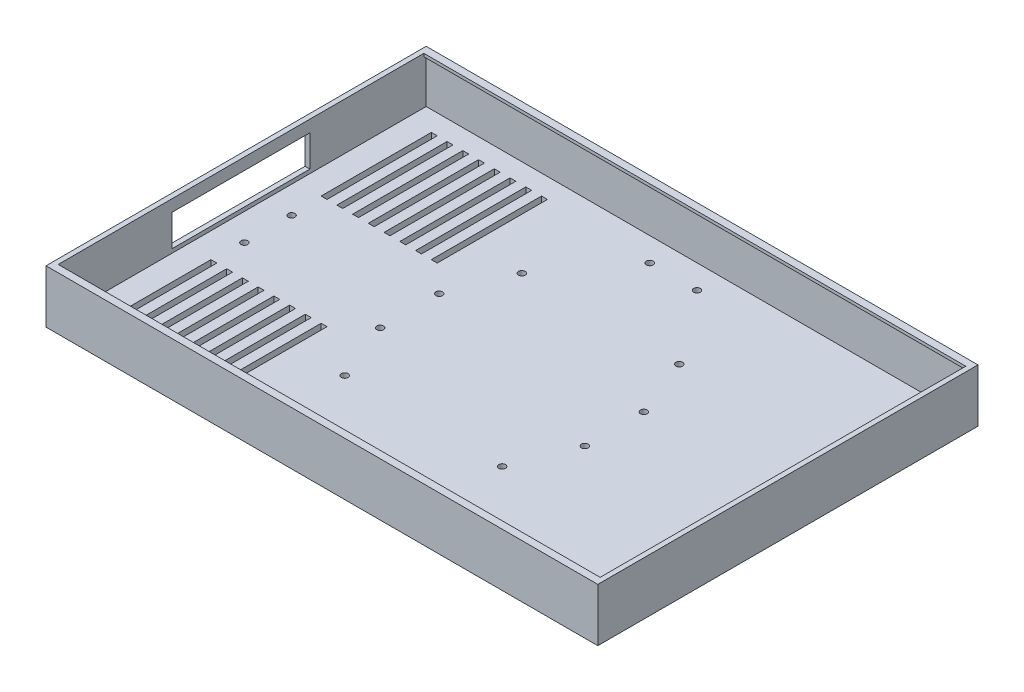
SolidWorks part; units mm, degrees
ref_plane "Front Plane" through (0, 0, 0) normal (0, 0, 1) x (1, 0, 0)
ref_plane "Top Plane" through (0, 0, 0) normal (0, 1, 0) x (1, 0, 0)
ref_plane "Right Plane" through (0, 0, 0) normal (1, 0, 0) x (0, 0, -1)
sketch "Sketch1" plane through (0, 0, 0) normal (0, 1, 0) x (1, 0, 0)
  line L1 (-140.2, -96.6) -> (140.2, -96.6)
  line L2 (-140.2, -96.6) -> (-140.2, 96.6)
  line L3 (-140.2, 96.6) -> (140.2, 96.6)
  line L4 (140.2, -96.6) -> (140.2, 96.6)
  line L5 (-140.2, -96.6) -> (140.2, 96.6) construction
  line L6 (-140.2, 96.6) -> (140.2, -96.6) construction
  dimension "D1" = 280.4
  dimension "D2" = 193.2
extrude "Shell Block" add sketch "Sketch1" along normal blind 27
ref_plane "Shell Front" through (0, 27, 0) normal (0, 1, 0) x (1, 0, 0)
sketch "Sketch2" plane through (0, 27, 0) normal (0, 1, 0) x (1, 0, 0)
  line L1 (-137.7, -92.9) -> (137.7, -92.9)
  line L2 (-137.7, -92.9) -> (-137.7, 92.9)
  line L3 (-137.7, 92.9) -> (137.7, 92.9)
  line L4 (137.7, -92.9) -> (137.7, 92.9)
  line L5 (-137.7, -92.9) -> (137.7, 92.9) construction
  line L6 (-137.7, 92.9) -> (137.7, -92.9) construction
  dimension "D1" = 275.4
  dimension "D2" = 185.8
extrude "Front Opening" cut sketch "Sketch2" against normal blind 1.5
ref_plane "Under Lip" through (0, 25.5, 0) normal (0, 1, 0) x (1, 0, 0)
sketch "Sketch3" plane through (0, 25.5, 0) normal (0, 1, 0) x (1, 0, 0)
  line L1 (-137.7, -94.1) -> (137.7, -94.1)
  line L2 (-137.7, -94.1) -> (-137.7, 94.1)
  line L3 (-137.7, 94.1) -> (137.7, 94.1)
  line L4 (137.7, -94.1) -> (137.7, 94.1)
  line L5 (-137.7, -94.1) -> (137.7, 94.1) construction
  line L6 (-137.7, 94.1) -> (137.7, -94.1) construction
  dimension "D1" = 275.4
  dimension "D2" = 188.2
extrude "Display Pocket" cut sketch "Sketch3" against normal blind 22.5
ref_plane "Back Inner" through (0, 3, 0) normal (0, 1, 0) x (1, 0, 0)
sketch "Sketch4" plane through (0, 3, 0) normal (0, 1, 0) x (1, 0, 0)
  line L1 (-69, 28) -> (-66, 28)
  line L2 (-69, 28) -> (-69, 84)
  line L3 (-69, 84) -> (-66, 84)
  line L4 (-66, 28) -> (-66, 84)
  line L6 (-69, -84) -> (-66, -84)
  line L7 (-69, -84) -> (-69, -28)
  line L8 (-69, -28) -> (-66, -28)
  line L9 (-66, -84) -> (-66, -28)
  line L11 (-77, 28) -> (-74, 28)
  line L12 (-77, 28) -> (-77, 84)
  line L13 (-77, 84) -> (-74, 84)
  line L14 (-74, 28) -> (-74, 84)
  line L16 (-77, -84) -> (-74, -84)
  line L17 (-77, -84) -> (-77, -28)
  line L18 (-77, -28) -> (-74, -28)
  line L19 (-74, -84) -> (-74, -28)
  line L21 (-85, 28) -> (-82, 28)
  line L22 (-85, 28) -> (-85, 84)
  line L23 (-85, 84) -> (-82, 84)
  line L24 (-82, 28) -> (-82, 84)
  line L26 (-85, -84) -> (-82, -84)
  line L27 (-85, -84) -> (-85, -28)
  line L28 (-85, -28) -> (-82, -28)
  line L29 (-82, -84) -> (-82, -28)
  line L31 (-93, 28) -> (-90, 28)
  line L32 (-93, 28) -> (-93, 84)
  line L33 (-93, 84) -> (-90, 84)
  line L34 (-90, 28) -> (-90, 84)
  line L36 (-93, -84) -> (-90, -84)
  line L37 (-93, -84) -> (-93, -28)
  line L38 (-93, -28) -> (-90, -28)
  line L39 (-90, -84) -> (-90, -28)
  line L41 (-101, 28) -> (-98, 28)
  line L42 (-101, 28) -> (-101, 84)
  line L43 (-101, 84) -> (-98, 84)
  line L44 (-98, 28) -> (-98, 84)
  line L46 (-101, -84) -> (-98, -84)
  line L47 (-101, -84) -> (-101, -28)
  line L48 (-101, -28) -> (-98, -28)
  line L49 (-98, -84) -> (-98, -28)
  line L51 (-109, 28) -> (-106, 28)
  line L52 (-109, 28) -> (-109, 84)
  line L53 (-109, 84) -> (-106, 84)
  line L54 (-106, 28) -> (-106, 84)
  line L56 (-109, -84) -> (-106, -84)
  line L57 (-109, -84) -> (-109, -28)
  line L58 (-109, -28) -> (-106, -28)
  line L59 (-106, -84) -> (-106, -28)
  line L61 (-117, 28) -> (-114, 28)
  line L62 (-117, 28) -> (-117, 84)
  line L63 (-117, 84) -> (-114, 84)
  line L64 (-114, 28) -> (-114, 84)
  line L66 (-117, -84) -> (-114, -84)
  line L67 (-117, -84) -> (-117, -28)
  line L68 (-117, -28) -> (-114, -28)
  line L69 (-114, -84) -> (-114, -28)
  line L71 (-125, 28) -> (-122, 28)
  line L72 (-125, 28) -> (-125, 84)
  line L73 (-125, 84) -> (-122, 84)
  line L74 (-122, 28) -> (-122, 84)
  line L76 (-125, -84) -> (-122, -84)
  line L77 (-125, -84) -> (-125, -28)
  line L78 (-125, -28) -> (-122, -28)
  line L79 (-122, -84) -> (-122, -28)
extrude "Vent Slots" cut sketch "Sketch4" against normal blind 4
sketch "Sketch5" plane through (0, 0, 0) normal (1, 0, 0) x (0, 0, -1)
  line L1 (-35, 5) -> (35, 5)
  line L2 (-35, 5) -> (-35, 21)
  line L3 (-35, 21) -> (35, 21)
  line L4 (35, 5) -> (35, 21)
extrude "Cable Exit (-X short side)" cut sketch "Sketch5" against normal blind 141.2
sketch "Sketch6" plane through (0, 3, 0) normal (0, 1, 0) x (1, 0, 0)
  circle A0 centre (-40, -45) radius 1.7
  circle A1 centre (-40, 45) radius 1.7
  circle A2 centre (40, -45) radius 1.7
  circle A3 centre (40, 45) radius 1.7
  circle A4 centre (-52, -15) radius 1.7
  circle A5 centre (-52, 15) radius 1.7
  circle A6 centre (52, -15) radius 1.7
  circle A7 centre (52, 15) radius 1.7
  circle A8 centre (-12, -82) radius 1.7
  circle A9 centre (-12, 82) radius 1.7
  circle A10 centre (12, -82) radius 1.7
  circle A11 centre (12, 82) radius 1.7
  circle A12 centre (-124, -12) radius 1.7
  circle A13 centre (-124, 12) radius 1.7
  circle A14 centre (124, -12) radius 1.7
  circle A15 centre (124, 12) radius 1.7
extrude "Bolt Holes" cut sketch "Sketch6" against normal blind 4
equation "\"DispL\" = 274.2"
equation "\"DispW\" = 187.0"
equation "\"DispT\" = 20.0"
equation "\"Clr\" = 0.6"
equation "\"Wall\" = 2.5"
equation "\"BackT\" = 3.0"
equation "\"CableRoom\" = 4.0"
equation "\"LipW\" = 1.2"
equation "\"LipT\" = 1.5"
equation "\"CableW\" = 70.0"
equation "\"CableH\" = 16.0"
equation "\"BoltD\" = 3.4"
equation "\"ShellL\" = \"DispL\" + 2 * \"Clr\" + 2 * \"Wall\""
equation "\"ShellW\" = \"DispW\" + 2 * \"Clr\" + 2 * \"Wall\""
equation "\"ShellH\" = \"BackT\" + \"DispT\" + \"CableRoom\""
equation "\"D1@Sketch1\" = \"ShellL\""
equation "\"D2@Sketch1\" = \"ShellW\""
equation "\"D1@Shell Block\" = \"ShellH\""
equation "\"D1@Shell Front\" = \"ShellH\""
equation "\"D1@Sketch2\" = \"DispL\" + 2 * \"Clr\""
equation "\"D2@Sketch2\" = \"DispW\" + 2 * \"Clr\" - 2 * \"LipW\""
equation "\"D1@Front Opening\" = \"LipT\""
equation "\"D1@Under Lip\" = \"ShellH\" - \"LipT\""
equation "\"D1@Sketch3\" = \"DispL\" + 2 * \"Clr\""
equation "\"D2@Sketch3\" = \"DispW\" + 2 * \"Clr\""
equation "\"D1@Display Pocket\" = \"ShellH\" - \"LipT\" - \"BackT\""
equation "\"D1@Back Inner\" = \"BackT\""
